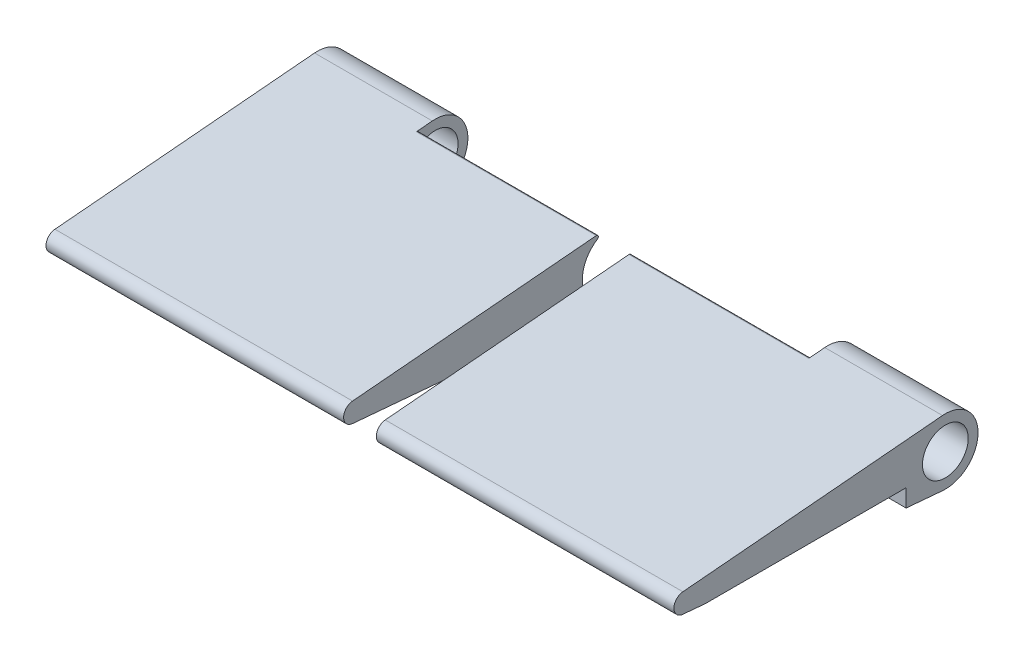
SolidWorks part; units mm, degrees
ref_plane "Front Plane" through (0, 0, 0) normal (0, 0, 1) x (1, 0, 0)
ref_plane "Top Plane" through (0, 0, 0) normal (0, 1, 0) x (1, 0, 0)
ref_plane "Right Plane" through (0, 0, 0) normal (1, 0, 0) x (0, 0, -1)
sketch "Sketch1" plane through (0, 0, 0) normal (1, 0, 0) x (0, 0, -1)
  line L0 (-40.1313, 1.4942) -> (-0.4375, 4.9808)
  line L1 (-40.1313, -1.4942) -> (-0.4375, -4.9808)
  circle A0 centre (0, 0) radius 5
  circle A1 centre (0, 0) radius 3.5
  circle A2 centre (-40, 0) radius 1.5
  dimension "D1" = 7
  dimension "D2" = 10
  dimension "D3" = 3
  dimension "D4" = 40
extrude "Boss-Extrude1" add sketch "Sketch1" along normal blind 27.5 contours A2 L1 A0 L0 | A2 region at (0, 0, 18.6105) region at (0, 0, 40)
extrude "Boss-Extrude2" add sketch "Sketch1<3>" against normal blind 18 contours A2 L1 A0 L0 | A2 | A0 A1 region at (0, 0, 18.6105) region at (0, 0, 40) region at (0, 3.5827, -3.2818)
sketch "Sketch1<3>" plane through (0, 0, 0) normal (1, 0, 0) x (0, 0, -1) same geometry as "Sketch1"
fillet "Fillet1" radius 0.3 2 edges at (13.75, -4.9808, 0.4375) (13.75, 4.9808, 0.4375)
sketch "Sketch2" plane through (0, 0, 0) normal (0, 0, 1) x (1, 0, 0)
  line L0 (-18, 5) -> (-18, -5) construction
  line L1 (0, -6.1303) -> (-18, -6.1303)
  line L2 (0, -6.1303) -> (0, -1.8)
  line L3 (0, -1.8) -> (-18, -1.8)
  line L4 (-18, -6.1303) -> (-18, -1.8)
  line L5 (-18, -5) -> (0, -5) construction
  dimension "D1" = 18
  dimension "D2" = 3.2
extrude "Cut-Extrude1" cut sketch "Sketch2" along normal blind 48 from offset 6
ref_plane "Plane1" through (30, 0, 0) normal (1, 0, 0) x (0, 0, -1)
mirror "Mirror2" about plane through (30, 0, 0) normal (1, 0, 0) of bodies 103
